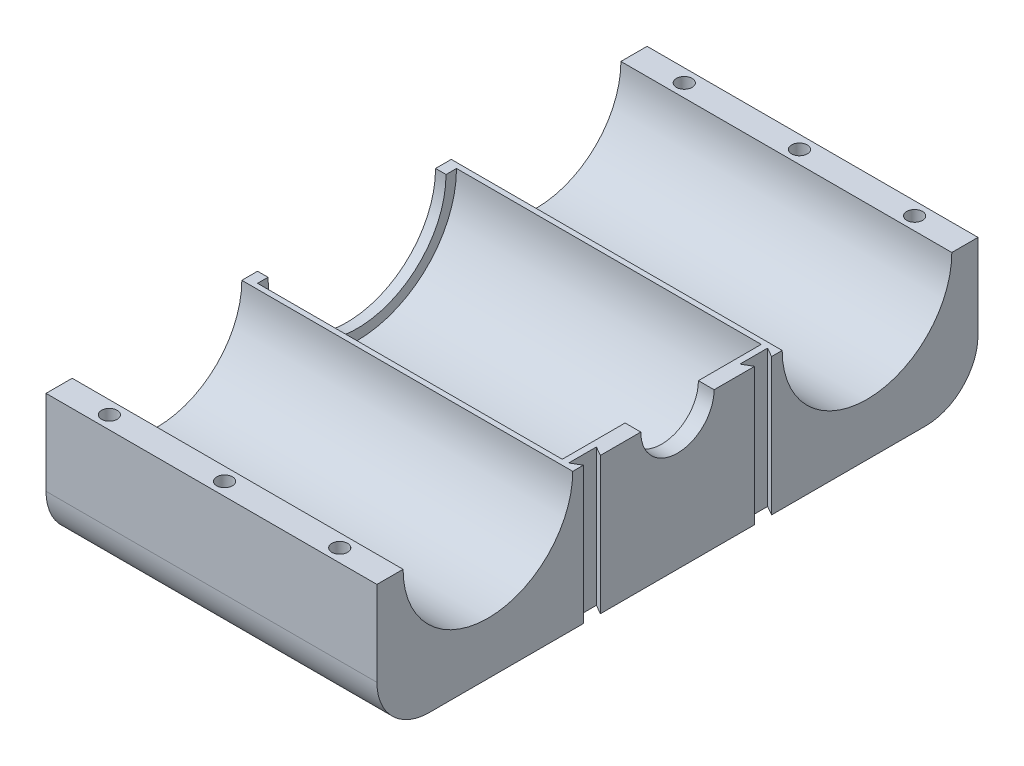
SolidWorks part; units mm, degrees
ref_plane "Front Plane" through (0, 0, 0) normal (0, 0, 1) x (1, 0, 0)
ref_plane "Top Plane" through (0, 0, 0) normal (0, 1, 0) x (1, 0, 0)
ref_plane "Right Plane" through (0, 0, 0) normal (1, 0, 0) x (0, 0, -1)
sketch "Sketch1" plane through (0, 0, 0) normal (1, 0, 0) x (0, 0, -1)
  line L0 (57.4, 42.0261) -> (57.4, 0) construction
  line L1 (0, 0) -> (114.8, 0)
  line L2 (0, 0) -> (0, 26.2)
  line L3 (114.8, 0) -> (114.8, 26.2)
  line L4 (0, 26.2) -> (5, 26.2) construction
  line L6 (37.4, 26.2) -> (77.4, 26.2) construction
  line L7 (37.4, 26.2) -> (77.4, 26.2)
  line L8 (0, 26.2) -> (5, 26.2)
  line L10 (37.4, 26.2) -> (77.4, 26.2)
  line L11 (109.8, 26.2) -> (114.8, 26.2)
  arc A0 (5, 26.2) -> (37.4, 26.2) centre (21.2, 26.2) ccw
  arc A1 (77.4, 26.2) -> (109.8, 26.2) centre (93.6, 26.2) ccw
  circle A2 centre (57.4, 13.245) radius 62.5 construction
  point P15 (93.6, 10)
  dimension "D4" = 16.2
  dimension "D3" = 16.2
  dimension "D6" = 125
  dimension "D1" = 5
  dimension "D5" = 10
  dimension "D2" = 40
extrude "Boss-Extrude1" add sketch "Sketch1" along normal blind 63.2 contours L8 L2 L1 L3 L7 region at (0, 10.7494, -57.4)
sketch "Sketch30" plane through (0, 26.2, 0) normal (0, 1, 0) x (1, 0, 0)
  line L0 (63.2, 57.4) -> (17.5829, 57.4) construction
  line L1 (63.2, 37.4) -> (63.2, 77.4) construction
  line L2 (63.2, 75.375) -> (61.4246, 76.4)
  line L3 (61.4246, 76.4) -> (61.4246, 71.1)
  line L4 (61.4246, 71.1) -> (63.2, 72.125)
  line L5 (63.2, 42.675) -> (61.4246, 43.7)
  line L6 (61.4246, 43.7) -> (61.4246, 38.4)
  line L7 (61.4246, 38.4) -> (63.2, 39.425)
  line L8 (63.2, 75.375) -> (63.2, 72.125)
  line L9 (63.2, 42.675) -> (63.2, 39.425)
  line L10 (63.2, 77.4) -> (0, 77.4) construction
  line L12 (63.2, 37.4) -> (0, 37.4) construction
  dimension "D1" = 5.3
  dimension "D2" = 60
  dimension "D3" = 60
  dimension "D4" = 3.25
  dimension "D5" = 60
  dimension "D6" = 1
  dimension "D7" = 1
extrude "Cut-Extrude14" cut sketch "Sketch30" against normal up to next
sketch "Sketch31" plane through (0, 0, 0) normal (-1, 0, 0) x (0, 0, 1)
  line L0 (-37.4, 26.2) -> (-77.4, 26.2) construction
  circle A0 centre (-57.4, 26.2) radius 19
  dimension "D1" = 38
extrude "Cut-Extrude15" cut sketch "Sketch31" against normal offset from surface (60.2 mm away) 3 contours A0 up to face at (63.2, 13.1, -57.4)
sketch "Sketch32" plane through (63.2, 0, 0) normal (1, 0, 0) x (0, 0, -1)
  line L0 (42.675, 26.2) -> (72.125, 26.2) construction
  circle A0 centre (57.4, 26.2) radius 7
  dimension "D1" = 14
extrude "Cut-Extrude16" cut sketch "Sketch32" against normal up to next
sketch "Sketch33" plane through (0, 0, 0) normal (-1, 0, 0) x (0, 0, 1)
  line L0 (-74.4, 26.2) -> (-76.4, 26.2)
  line L1 (-40.4, 26.2) -> (-38.4, 26.2)
  arc A1 (-76.4, 26.2) -> (-38.4, 26.2) centre (-57.4, 26.2) ccw construction
  arc A2 (-74.4, 26.2) -> (-40.4, 26.2) centre (-57.4, 26.2) ccw
  arc A3 (-74.4, 26.2) -> (-40.4, 26.2) centre (-57.4, 26.2) ccw
  arc A4 (-76.4, 26.2) -> (-38.4, 26.2) centre (-57.4, 26.2) ccw
  dimension "D1" = 2
extrude "Boss-Extrude6" add sketch "Sketch33" against normal blind 2
fillet "Fillet1" radius 10 2 edges at (31.6, 0, -114.8) (31.6, 0, 0)
sketch "Sketch34" plane through (0, 26.2, 0) normal (0, 1, 0) x (1, 0, 0)
  line L0 (0, 112.3) -> (63.2, 112.3) construction
  line L1 (0, 109.8) -> (0, 114.8) construction
  line L2 (63.2, 109.8) -> (63.2, 114.8) construction
  line L3 (63.2, 57.4) -> (76.2618, 57.4) construction
  line L4 (63.2, 50.4) -> (63.2, 64.4) construction
  circle A0 centre (9.6, 112.3) radius 1.5
  circle A1 centre (31.6, 112.3) radius 1.5
  circle A2 centre (53.6, 112.3) radius 1.5
  circle A3 centre (53.6, 2.5) radius 1.5
  circle A4 centre (31.6, 2.5) radius 1.5
  circle A5 centre (9.6, 2.5) radius 1.5
  dimension "D1" = 3
  dimension "D2" = 22
  dimension "D3" = 22
extrude "Cut-Extrude17" cut sketch "Sketch34" against normal blind 15
sketch "Sketch35" plane through (0, 0, 0) normal (0, -1, 0) x (1, 0, 0)
  line L0 (31.6, -10) -> (31.6, -104.8) construction
  line L1 (16.0672, -30.106) -> (47.1328, -30.106) construction
  line L2 (16.0672, -30.106) -> (16.0672, -86.0987) construction
  line L3 (16.0672, -86.0987) -> (47.1328, -86.0987) construction
  line L4 (47.1328, -30.106) -> (47.1328, -86.0987) construction
  line L5 (63.2, -10) -> (0, -10) construction
  line L6 (0, -104.8) -> (63.2, -104.8) construction
  circle A0 centre (16.0672, -30.106) radius 2.3
  circle A1 centre (47.1328, -30.106) radius 2.3
  circle A2 centre (16.0672, -86.0987) radius 2.3
  circle A3 centre (47.1328, -86.0987) radius 2.3
  point P8 (31.6, -30.106)
  dimension "D1" = 4.6
  dimension "D2" = 4.6
  dimension "D3" = 4.6
  dimension "D4" = 4.6
extrude "Cut-Extrude18" cut sketch "Sketch35" against normal blind 6
equation "\"MotorDIA\"= 37' Motor Diameter"
equation "\"SyringeDIA\"= 31.4'60ml Syringe Diameter"
equation "\"MotorShaftDIA\"= 6'Motor Shaft Dia"
equation "\"MotorKeyway\"= 1'Motor Shaft Keyway Depth"
equation "\"MotorLength\"= 56.7'Motor Length Excluding Shaft"
equation "\"SyringeLength\"= 117.3'60ml Syringe Length Excluding Nozzle"
equation "\"3Dtol\"= .5'Sizing Tolerance for 3D printed parts"
equation "\"ChamberDIA\"= 100 - 4'Buoyancy Chamber inner Diameter"
equation "\"ChamberThk\"= 2mm'Buoyancy Chamber Wall Thickness"
equation "\"D4@Sketch1\"=\"SyringeDIA\"/2+\"3Dtol\""
equation "\"D1@Boss-Extrude1\"=\"MotorLength\"+\"3Dtol\"+4"
equation "\"D4@Sketch8\"=\"D1@Sketch8\""
equation "\"BearingOD\"= 10"
equation "\"BearingID\"= 4"
equation "\"Bearingwidth\"= 4"
equation "\"ShaftDIA\"= 4"
equation "\"D2@Sketch22\"=\"D3@Sketch22\"/5"
equation "\"D4@Sketch22\"=\"D2@Sketch22\""
equation "\"D5@Sketch22\"=\"D4@Sketch22\""
equation "\"D6@Sketch22\"=\"D5@Sketch22\""
equation "\"D3@Sketch1\"=\"D4@Sketch1\""
